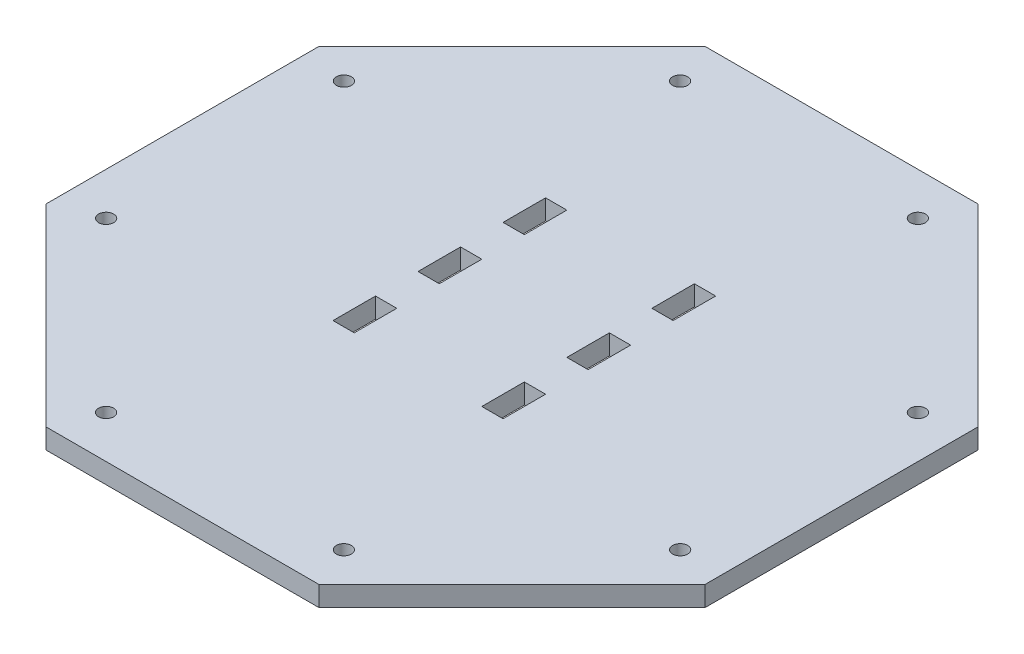
SolidWorks part; units mm, degrees
material "Custom Plastic"
ref_plane "Front Plane" through (0, 0, 0) normal (0, 0, 1) x (1, 0, 0)
ref_plane "Top Plane" through (0, 0, 0) normal (0, 1, 0) x (1, 0, 0)
ref_plane "Right Plane" through (0, 0, 0) normal (1, 0, 0) x (0, 0, -1)
ref_axis "Axis1" through (0, 6.2941, 0) along (0, -1, 0)
sketch "Sketch1" plane through (0, 0, 0) normal (0, 1, 0) x (1, 0, 0)
  line L1 (-40.769, 98.425) -> (-98.425, 40.769)
  line L2 (-98.425, 40.769) -> (-98.425, -40.769)
  line L3 (-98.425, -40.769) -> (-40.769, -98.425)
  line L4 (-40.769, -98.425) -> (40.769, -98.425)
  line L5 (40.769, -98.425) -> (98.425, -40.769)
  line L6 (98.425, -40.769) -> (98.425, 40.769)
  line L7 (98.425, 40.769) -> (40.769, 98.425)
  line L8 (40.769, 98.425) -> (-40.769, 98.425)
  circle A0 centre (0, 0) radius 98.425 construction
  dimension "D1" = 196.85
extrude "Base" add sketch "Sketch1" along normal blind 5.9944
sketch "Sketch2" plane through (0, 5.9944, 0) normal (0, 1, 0) x (1, 0, 0)
  line L0 (40.769, 98.425) -> (-40.769, 98.425) construction
  line L1 (35.5085, 85.725) -> (-35.5085, 85.725)
  line L2 (-35.5085, 85.725) -> (-85.725, 35.5085)
  line L3 (-85.725, 35.5085) -> (-85.725, -35.5085)
  line L4 (-85.725, -35.5085) -> (-35.5085, -85.725)
  line L5 (-35.5085, -85.725) -> (35.5085, -85.725)
  line L6 (35.5085, -85.725) -> (85.725, -35.5085)
  line L7 (85.725, -35.5085) -> (85.725, 35.5085)
  line L8 (85.725, 35.5085) -> (35.5085, 85.725)
  circle A0 centre (0, 0) radius 85.725 construction
  dimension "D1" = 12.7
hole_wizard "Mounting holes" positions "Sketch4" profile "Sketch3" hole size "#8" standard "ANSI Inch"
sketch "Sketch4" plane through (0, 5.9944, 0) normal (0, 1, 0) x (1, 0, 0)
  point P0 (-35.5085, 85.725)
  point P8 (35.5085, 85.725)
  point P11 (85.725, 35.5085)
  point P14 (85.725, -35.5085)
  point P17 (35.5085, -85.725)
  point P20 (-35.5085, -85.725)
  point P23 (-85.725, -35.5085)
  point P26 (-85.725, 35.5085)
sketch "Sketch3" plane through (-35.5085, 5.9944, -85.725) normal (1, 0, 0) x (0, 0, 1)
  line L0 (0, 0) -> (0, 5.9944)
  line L1 (0, 5.9944) -> (2.2479, 5.9944)
  line L2 (2.2479, 5.9944) -> (2.2479, 0)
  line L5 (2.2479, 0) -> (0, 0)
  line L10 (0, 5.9944) -> (-2.2479, 5.9944) construction
  line L11 (0, -6.35) -> (0, 107.95) construction
  dimension "Hole Dia." = 4.4958
  dimension "Hole Depth" = 5.9944
  dimension "Drill Angle" = 180
sketch "Sketch5" plane through (0, 5.9944, 0) normal (0, 1, 0) x (1, 0, 0)
  line L0 (0, 98.425) -> (0, -98.425) construction
  line L1 (40.769, 98.425) -> (-40.769, 98.425) construction
  line L2 (-40.769, -98.425) -> (40.769, -98.425) construction
  line L3 (0, 0) -> (-25.4, 0) construction
  line L4 (-25.4, 0) -> (-25.4, 35.433) construction
  line L5 (-25.4, 0) -> (-25.4, -35.433) construction
  line L6 (-25.4, 10.033) -> (-25.4, -2.667)
  line L7 (-25.4, 35.433) -> (-19.05, 35.433)
  line L8 (-25.4, 35.433) -> (-25.4, 22.733)
  line L9 (-25.4, 22.733) -> (-19.05, 22.733)
  line L10 (-19.05, 35.433) -> (-19.05, 22.733)
  line L11 (-19.05, 10.033) -> (-19.05, -2.667)
  line L12 (-25.4, 10.033) -> (-19.05, 10.033)
  line L13 (-25.4, -2.667) -> (-19.05, -2.667)
  line L14 (-25.4, -15.367) -> (-25.4, -28.067)
  line L15 (-19.05, -15.367) -> (-19.05, -28.067)
  line L16 (-25.4, -15.367) -> (-19.05, -15.367)
  line L17 (-25.4, -28.067) -> (-19.05, -28.067)
  line L18 (25.4, 0) -> (25.4, -35.433) construction
  line L19 (25.4, 0) -> (25.4, 35.433) construction
  line L20 (25.4, -28.067) -> (19.05, -28.067)
  line L21 (25.4, -15.367) -> (19.05, -15.367)
  line L22 (19.05, -15.367) -> (19.05, -28.067)
  line L23 (25.4, -15.367) -> (25.4, -28.067)
  line L24 (25.4, -2.667) -> (19.05, -2.667)
  line L25 (25.4, 10.033) -> (19.05, 10.033)
  line L26 (19.05, 10.033) -> (19.05, -2.667)
  line L27 (19.05, 35.433) -> (19.05, 22.733)
  line L28 (25.4, 22.733) -> (19.05, 22.733)
  line L29 (25.4, 35.433) -> (25.4, 22.733)
  line L30 (25.4, 35.433) -> (19.05, 35.433)
  line L31 (25.4, 10.033) -> (25.4, -2.667)
  dimension "D1" = 25.4
  dimension "D2" = 62.992
  dimension "D3" = 6.35
  dimension "D4" = 12.7
  dimension "D6" = 12.7
  dimension "D5" = 3
extrude "Cut-Extrude1" cut sketch "Sketch5" against normal through all
equation "\"MAT_THICKNESS\"=0.236"
equation "\"D1@Base\"=\"MAT_THICKNESS\""
